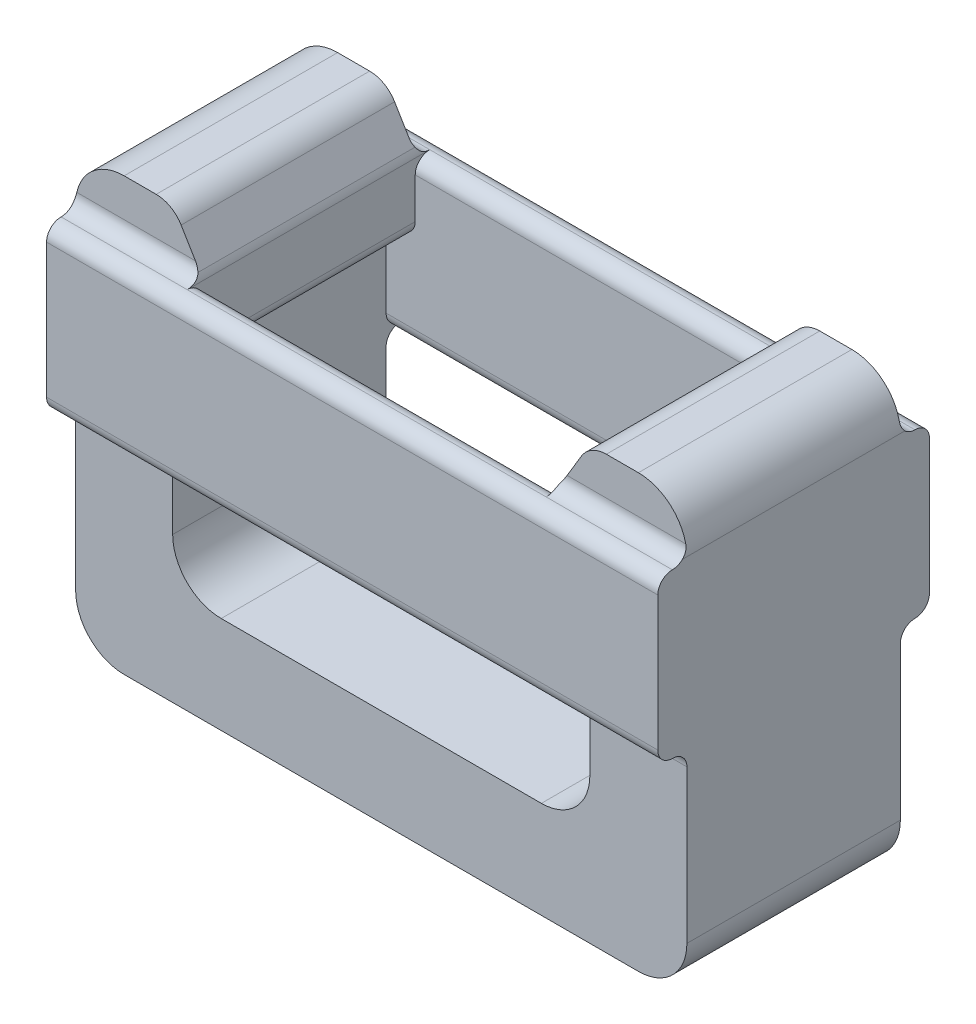
SolidWorks part; units mm, degrees
ref_plane "Front Plane" through (0, 0, 0) normal (1, 0, 0) x (0, 1, 0)
ref_plane "Top Plane" through (0, 0, 0) normal (0, 0, 1) x (0, 1, 0)
ref_plane "Right Plane" through (0, 0, 0) normal (0, 1, 0) x (-1, 0, 0)
sketch "Sketch1" plane through (0, 0, 0) normal (0, 0, 1) x (0, 1, 0)
  line L0 (0, 0) -> (44.5126, 0)
  line L1 (44.5126, 0) -> (44.5126, 10)
  line L2 (44.5126, 10) -> (39.5126, 13)
  line L3 (39.5126, 13) -> (31.9256, 13)
  line L4 (31.9256, 13) -> (31.9256, 10)
  line L5 (31.9256, 10) -> (10, 10)
  line L6 (10, 10) -> (10, 53)
  line L7 (0, 0) -> (0, 63)
  line L8 (0, 31.5) -> (10, 31.5) construction
  line L9 (31.9256, 53) -> (10, 53)
  line L10 (31.9256, 50) -> (31.9256, 53)
  line L11 (39.5126, 50) -> (31.9256, 50)
  line L12 (44.5126, 53) -> (39.5126, 50)
  line L13 (44.5126, 63) -> (44.5126, 53)
  line L14 (0, 63) -> (44.5126, 63)
  dimension "D3" = 12.587
  dimension "D4" = 5
  dimension "D2" = 10
  dimension "D6" = 10
  dimension "D7" = 3
  dimension "D5" = 43
  dimension "D1" = 34.5126
extrude "Boss-Extrude1" add sketch "Sketch1" along normal blind 22
fillet "Fillet2" radius 5 4 edges at (-63, 0, 11) (-63, 44.5126, 11) (0, 0, 11) (0, 44.5126, 11)
fillet "Fillet4" radius 5 2 edges at (-53, 10, 11) (-10, 10, 11)
fillet "Fillet5" radius 1.5 2 edges at (-53, 31.9256, 11) (-10, 31.9256, 11)
fillet "Fillet6" radius 3 2 edges at (-53, 44.5126, 11) (-10, 44.5126, 11)
fillet "Fillet7" radius 1.5 4 edges at (-13, 39.5126, 11) (-50, 39.5126, 11) (-50, 31.9256, 11) (-13, 31.9256, 11)
sketch "Sketch5" plane through (0, 0, 22) normal (0, 0, 1) x (1, 0, 0)
  line L0 (-50, 39.0971) -> (-63, 39.0971) construction
  line L1 (-63, 39.5126) -> (-63, 5) construction
  line L2 (-50, 39.0971) -> (0, 39.0971) construction
  line L3 (0, 5) -> (0, 39.5126) construction
  line L5 (-63, 39.0971) -> (0, 39.0971)
  line L6 (-63, 39.0971) -> (-63, 22.2563)
  line L7 (-63, 22.2563) -> (0, 22.2563)
  line L8 (0, 39.0971) -> (0, 22.2563)
extrude "Boss-Extrude2" add sketch "Sketch5" along normal blind 3 contours L6 L5 L8 L7
sketch "Sketch6" plane through (0, 0, 0) normal (0, 0, -1) x (1, 0, 0)
  line L0 (0, -5) -> (0, -39.5126) construction
  line L1 (-63, -39.0971) -> (0, -39.0971)
  line L2 (-63, -39.0971) -> (-63, -22.2563)
  line L3 (-63, -22.2563) -> (0, -22.2563)
  line L4 (0, -39.0971) -> (0, -22.2563)
extrude "Boss-Extrude3" add sketch "Sketch6" along normal blind 3
fillet "Fillet8" radius 1.5 8 edges at (-31.5, 22.2563, 22) (-31.5, 22.2563, 25) (-31.5, 39.0971, 25) (-31.5, 39.0971, 22) (-31.5, 22.2563, 0) (-31.5, 39.0971, 0) (-31.5, 22.2563, -3) (-31.5, 39.0971, -3)
fillet "Fillet9" radius 1.5 8 edges at (-58, 22.2563, 22) (-5, 22.2563, 22) (-56.5, 39.0971, 22) (-6.5, 39.0971, 22) (-6.5, 39.0971, 0) (-5, 22.2563, 0) (-58, 22.2563, 0) (-56.5, 39.0971, 0)
equation "\"b\"= 20mm"
equation "\"h\"= 10mm"
equation "\"gamma\"= 3mm"
equation "\"E\"= 2.32"
equation "\"F_t\"= 1.112055"
equation "\"F_s\"= 22.24"
equation "\"L\"= ( ( \"E\" * ( \"h\" ^ 3 ) * \"b\" * ( \"gamma\" ) ) / ( 4 * ( \"F_t\" ) ) ) ^ ( 1 / 3 )"
equation "\"D2@Sketch1\"=\"h\""
equation "\"D6@Sketch1\"=\"h\""
equation "\"D1@Boss-Extrude1\"=\"b\"+2"
equation "\"x_min\"= ( \"F_s\" / ( 2 * \"b\" * 0.046 ) )"
equation "\"D7@Sketch1\"=\"gamma\""
equation "\"D3@Sketch1\"=\"x_min\"+0.5mm"
equation "\"D1@Sketch1\"=\"L\"+3mm"
equation "\"D5@Sketch1\"=\"gamma\"*4+\"h\"*3+1"
